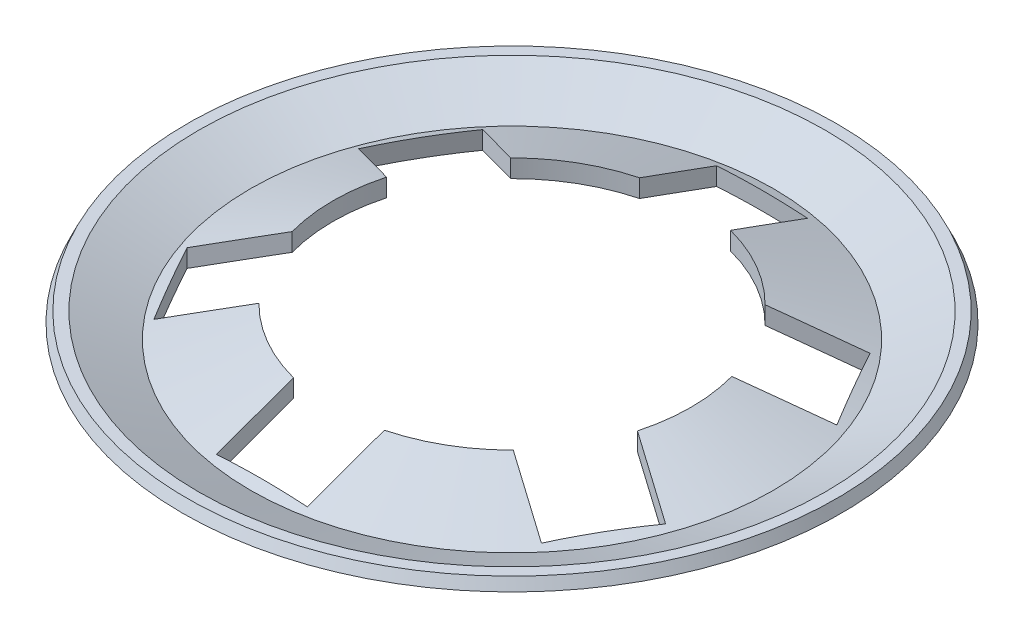
SolidWorks part; units mm, degrees
material "Galvanized Steel"
ref_plane "Front Plane" through (0, 0, 0) normal (0, 0, 1) x (1, 0, 0)
ref_plane "Top Plane" through (0, 0, 0) normal (0, 1, 0) x (1, 0, 0)
ref_plane "Right Plane" through (0, 0, 0) normal (1, 0, 0) x (0, 0, -1)
sketch "Sketch2" plane through (0, 0, 0) normal (0, 0, 1) x (1, 0, 0)
  line L0 (-4, 1.0883) -> (-5.842, 0.4014)
  line L1 (-5.842, 0.4014) -> (-7.0032, 0.9516)
  line L2 (-7.0032, 0.9516) -> (-7.2572, 0.9516)
  line L3 (-7.2572, 0.9516) -> (-7.366, 0.722)
  line L4 (-7.366, 0.722) -> (-5.842, 0)
  line L5 (-5.842, 0) -> (-4, 0.6869)
  line L6 (-4, 0.6869) -> (-4, 1.0883)
  line L7 (0, 0) -> (0, 5.5064) construction
  line L8 (0, 0) -> (-4.0763, 0) construction
  dimension "D1" = 0.3761
  dimension "D2" = 14.732
  dimension "D3" = 0.3627
  dimension "D4" = 25.35
  dimension "D5" = 25.35
  dimension "D6" = 0.1087
  dimension "D7" = 11.684
  dimension "D8" = 8
  dimension "D10" = 20.45
revolve "Revolve1" add sketch "Sketch2" angle 360 about L7
ref_axis "Axis2" through (0, 1.0883, 0) along (0, -1, 0)
sketch "Sketch3" plane through (0, 0, 0) normal (0, 1, 0) x (1, 0, 0)
  line L0 (1.016, 5.588) -> (1.016, 0)
  line L1 (-1.016, 5.588) -> (1.016, 5.588)
  line L2 (-1.016, 0) -> (-1.016, 5.588)
  line L3 (0, 0) -> (0, 7.9655) construction
  line L4 (-1.016, 0) -> (1.016, 0)
  dimension "D1" = 5.588
  dimension "D2" = 2.032
extrude "Extrude1" cut sketch "Sketch3" along normal through all
pattern_circular "CirPattern1" count 6 over 360 about axis through (0, 1.0883, 0) along (0, -1, 0) of "Extrude1"
